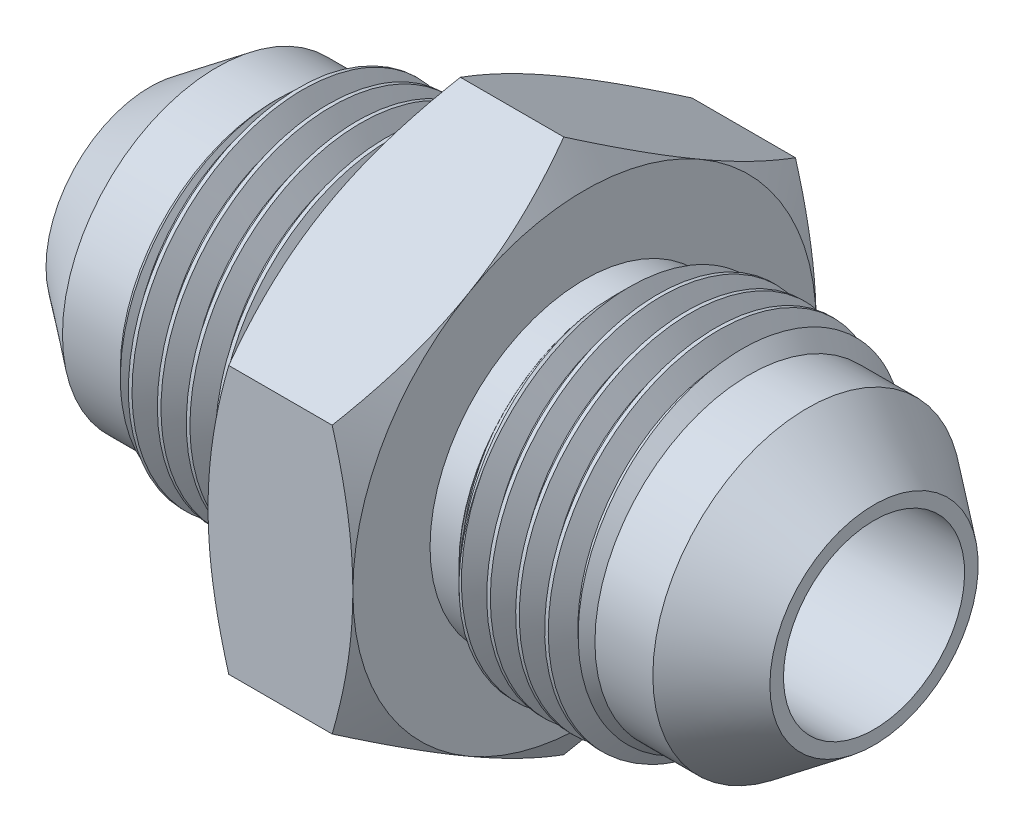
SolidWorks part; units mm, degrees
note: '?' marks a value the reader was unsure of.
material "AISI 321 Annealed Stainless Steel (SS)"
ref_plane "Front" through (0, 0, 0) normal (0, 0, 1) x (1, 0, 0)
ref_plane "Top" through (0, 0, 0) normal (0, 1, 0) x (1, 0, 0)
ref_plane "Right" through (0, 0, 0) normal (1, 0, 0) x (0, 0, -1)
sketch "Sketch6" plane through (0, 0, 0) normal (0, 0, 1) x (1, 0, 0)
  line L1 (19.8438, 9.525) -> (19.8438, -9.525) construction
  line L2 (-19.8438, 0) -> (19.8438, 0)
  line L4 (-19.8438, 0) -> (-19.8438, 9.525)
  line L5 (-19.8438, 9.525) -> (19.8438, 9.525)
  line L6 (19.8438, 0) -> (19.8438, 9.525)
  point P4 (3.9688, 0)
  point P6 (-3.9688, 0)
  dimension "Straight Dia" = 19.05
  dimension "Length" = 39.6875
  dimension "L1" = 15.875
  dimension "D1" = 15.875
revolve "Revolve3" add sketch "Sketch6" angle 360 about L2
sketch "Sketch14" plane through (-19.8438, 0, 0) normal (-1, 0, 0) x (0, 0, 1)
  circle A1 centre (0, 0) radius 9.525
  circle A2 centre (0, 0) radius 9.525
  dimension "D1" = 0
curve "Helix/Spiral1" pitch 1.5875 height 17.4625 turns 11 parameters "Pitch"=1.5875
sketch "Sketch15" plane through (0, 0, 0) normal (0, 0, 1) x (1, 0, 0)
  line L0 (-21.2328, 9.525) -> (-19.8438, 9.525)
  line L1 (-19.8438, 9.525) -> (-20.4391, 8.4939)
  line L2 (-20.4391, 8.4939) -> (-20.6375, 8.4939)
  line L3 (-20.6375, 8.4939) -> (-21.2328, 9.525)
  line L4 (-20.5383, 8.4939) -> (-20.5383, 9.525) construction
  line L5 (-20.9352, 9.0094) -> (-20.1414, 9.0094) construction
  dimension "D1" = 60
  dimension "D2" = 0.1984
  dimension "D3" = 0.7937
sweep "Cut-Sweep1" cut profiles "Sketch15" path "Helix/Spiral1" align with end faces yes
sketch "Sketch16" plane through (0, 0, 0) normal (1, 0, 0) x (0, 0, -1)
  line L0 (-9.525, 0) -> (9.525, 0) construction
  circle A0 centre (0, 0) radius 9.525 construction
ref_axis "Axis1" through (0, 0, 9.525) along (0, 0, -1)?
pattern_circular "CirPattern1" count 2 every 180 about axis through (0, 0, 9.525) along (0, 0, -1) of "Cut-Sweep1"
ref_plane "Plane1" through (-3.9688, 0, 0) normal (1, 0, 0) x (0, 0, -1)
sketch "Sketch12" plane through (-3.9688, 0, 0) normal (1, 0, 0) x (0, 0, -1)
  line L1 (0, 14.6647) -> (-12.7, 7.3323)
  line L2 (-12.7, 7.3323) -> (-12.7, -7.3323)
  line L3 (-12.7, -7.3323) -> (0, -14.6647)
  line L4 (0, -14.6647) -> (12.7, -7.3323)
  line L5 (12.7, -7.3323) -> (12.7, 7.3323)
  line L6 (12.7, 7.3323) -> (0, 14.6647)
  circle A0 centre (0, 0) radius 12.7 construction
  dimension "Hex" = 25.4
extrude "Extrude1" add sketch "Sketch12" along normal up to vertex (7.9375 mm away) up to point (3.9688, 0, 0)
sketch "Sketch7" plane through (0, 0, 0) normal (0, 0, 1) x (1, 0, 0)
  line L0 (-19.8438, 0) -> (-19.8438, 4.9657)
  line L2 (-19.8438, 4.9657) -> (19.8438, 4.9657)
  line L4 (19.8438, 0) -> (19.8438, 9.525) construction
  line L11 (19.8438, 4.9657) -> (19.8438, 0)
  line L12 (19.8438, 0) -> (-19.8438, 0)
  line L13 (-19.8438, 4.9657) -> (-19.8438, -4.9657) construction
  dimension "ID" = 9.9314
sketch "Sketch10" plane through (0, 0, 0) normal (0, 0, 1) x (1, 0, 0)
  line L0 (-19.8438, 9.525) -> (19.8438, 9.525) construction
  line L1 (-11.0245, -9.525) -> (-11.0245, 9.525) construction
  line L2 (-19.8438, 0) -> (-19.8438, 9.525) construction
  line L3 (-6.6128, 9.525) -> (-5.5563, 8.4685)
  line L4 (-21.2328, 9.525) -> (-19.8438, 9.525) construction
  line L5 (0, 0) -> (-19.8438, 0) construction
  line L6 (6.6128, 9.525) -> (3.9688, 9.525)
  line L8 (-5.5563, 8.4685) -> (-3.9688, 8.4685)
  line L9 (3.9688, 8.4685) -> (3.9688, 9.525)
  line L11 (0, 0) -> (0, 14.6647) construction
  line L12 (3.9688, 14.6647) -> (-3.9688, 14.6647) construction
  line L13 (-19.8438, 5.7106) -> (-19.8438, 9.525)
  line L14 (-16.1838, 8.4685) -> (-19.8438, 5.7106)
  line L15 (-13.0088, 8.4685) -> (-16.1838, 8.4685)
  line L16 (-11.9523, 9.525) -> (-13.0088, 8.4685)
  line L17 (-19.8438, 9.525) -> (-11.9523, 9.525)
  line L18 (-3.9688, 8.4685) -> (-3.9688, 9.525)
  line L19 (-6.6128, 9.525) -> (-3.9688, 9.525)
  line L20 (-3.9688, -12.7) -> (-3.9688, 12.7) construction
  line L21 (19.8438, 9.525) -> (11.9523, 9.525)
  line L22 (11.9523, 9.525) -> (13.0088, 8.4685)
  line L23 (13.0088, 8.4685) -> (16.1838, 8.4685)
  line L24 (16.1838, 8.4685) -> (19.8438, 5.7106)
  line L25 (19.8438, 5.7106) -> (19.8438, 9.525)
  line L26 (5.5563, 8.4685) -> (3.9688, 8.4685)
  line L27 (6.6128, 9.525) -> (5.5563, 8.4685)
  point P9 (-11.0245, -9.525)
  point P24 (-11.0245, 0)
  dimension "D3" = 3.175
  dimension "D4" = 37
  dimension "D5" = 1.5875
  dimension "D6" = 45
  dimension "D1" = 11.4211
  dimension "D7" = 45
  dimension "D8" = 1.9844
revolve "Cut-Revolve6" cut sketch "Sketch10" angle 360 about L2
revolve "Cut-Revolve5" cut sketch "Sketch7" angle 360 about L12
sketch "Sketch13" plane through (0, 0, 0) normal (0, 0, 1) x (1, 0, 0)
  line L0 (-3.9688, 14.6647) -> (-3.9688, 12.7)
  line L1 (-3.9688, 7.3323) -> (-3.9688, 14.6647) construction
  line L2 (-3.9688, 12.7) -> (-2.8344, 14.6647)
  line L3 (-2.8344, 14.6647) -> (-3.9688, 14.6647)
  line L4 (2.8344, 14.6647) -> (3.9688, 12.7)
  line L5 (3.9688, 14.6647) -> (3.9688, 7.3323) construction
  line L6 (3.9688, 12.7) -> (3.9688, 14.6647)
  line L7 (3.9688, 14.6647) -> (2.8344, 14.6647)
  dimension "D2" = 30
revolve "Cut-Revolve7" cut sketch "Sketch13" angle 360 about L2
equation "\"D3@Helix/Spiral1\" = \"L1@Sketch6\"+\"Pitch@Helix/Spiral1\""
equation "\"D2@Sketch15\" = \"Pitch@Helix/Spiral1\"*.125"
equation "\"D3@Sketch15\" = \"Pitch@Helix/Spiral1\"*.5"
equation "\"D3@Sketch10\" = \"Pitch@Helix/Spiral1\"*2"
equation "\"D5@Sketch10\" = \"Pitch@Helix/Spiral1\""
equation "\"D1@Sketch10\" = \"ID@Sketch7\"*1.15"
equation "\"D1@Sketch6\" = \"L1@Sketch6\""
equation "\"D8@Sketch10\" = \"Pitch@Helix/Spiral1\"*1.25"
